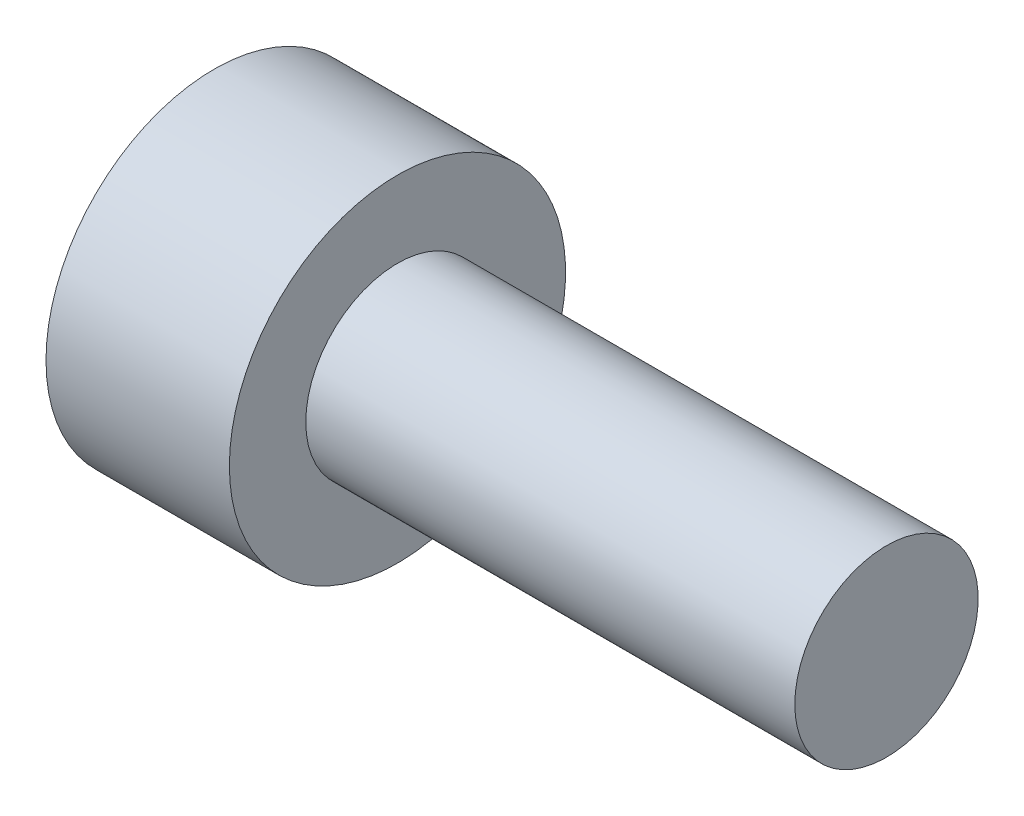
SolidWorks part; units mm, degrees
ref_plane "Front Plane" through (0, 0, 0) normal (0, 0, 1) x (1, 0, 0)
ref_plane "Top Plane" through (0, 0, 0) normal (0, 1, 0) x (1, 0, 0)
ref_plane "Right Plane" through (0, 0, 0) normal (1, 0, 0) x (0, 0, -1)
sketch "Screw Sketch" plane through (0, 0, 0) normal (0, 0, 1) x (1, 0, 0)
  line L0 (-1000, 0) -> (1000, 0) construction
  line L1 (-3, 0) -> (-3, 2.75)
  line L2 (-3, 2.75) -> (0, 2.75)
  line L3 (0, 2.75) -> (0, 1.5)
  line L4 (0, 1.5) -> (8, 1.5)
  line L5 (8, 1.5) -> (8, 0)
  line L6 (8, 0) -> (-3, 0)
revolve "Screw" add sketch "Screw Sketch" angle 360 about L0
ref_axis "Engine Axis" through (8.55, 0, 0) along (-1, 0, 0)
ref_plane "Head Top" through (-3, 0, 0) normal (1, 0, 0) x (0, 0, -1)
sketch "Socket Sketch" plane through (-3, 0, 0) normal (1, 0, 0) x (0, 0, -1)
  line L0 (1.4434, 0) -> (0.7217, 1.25)
  line L1 (0.7217, 1.25) -> (-0.7217, 1.25)
  line L2 (-0.7217, 1.25) -> (-1.4434, 0)
  line L3 (-1.4434, 0) -> (-0.7217, -1.25)
  line L4 (-0.7217, -1.25) -> (0.7217, -1.25)
  line L5 (0.7217, -1.25) -> (1.4434, 0)
extrude "Socket" cut sketch "Socket Sketch" along normal blind 1.5
